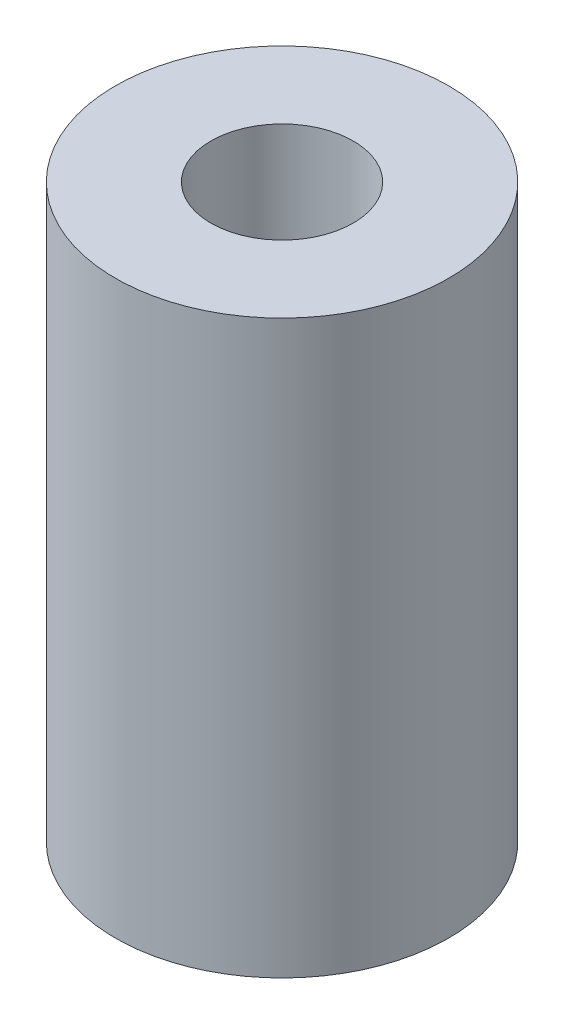
SolidWorks part; units mm, degrees
ref_plane "Front Plane" through (0, 0, 0) normal (0, 0, 1) x (1, 0, 0)
ref_plane "Top Plane" through (0, 0, 0) normal (0, 1, 0) x (1, 0, 0)
ref_plane "Right Plane" through (0, 0, 0) normal (1, 0, 0) x (0, 0, -1)
sketch "Sketch1" plane through (0, 0, 0) normal (0, 1, 0) x (1, 0, 0)
  circle A1 centre (0, 0) radius 4.445
  dimension "D1" = 8.89
extrude "Boss-Extrude1" add sketch "Sketch1" along normal blind 15.24
hole_wizard "#6 Clearance Hole1" positions "Sketch2" profile "Sketch3" hole size "#6" standard "ANSI Inch" end condition through all
sketch "Sketch2" plane through (0, 15.24, 0) normal (0, 1, 0) x (1, 0, 0)
  point P0 (0, 0)
sketch "Sketch3" plane through (0, 15.24, 0) normal (1, 0, 0) x (0, 0, 1)
  line L0 (0, 0) -> (0, 15.24)
  line L1 (0, 15.24) -> (1.8986, 15.24)
  line L2 (1.8986, 15.24) -> (1.8986, 0)
  line L5 (1.8986, 0) -> (0, 0)
  line L11 (0, -6.35) -> (0, 107.95) construction
  dimension "Thru Hole Dia." = 3.7973
  dimension "Thru Hole Depth" = 15.24
